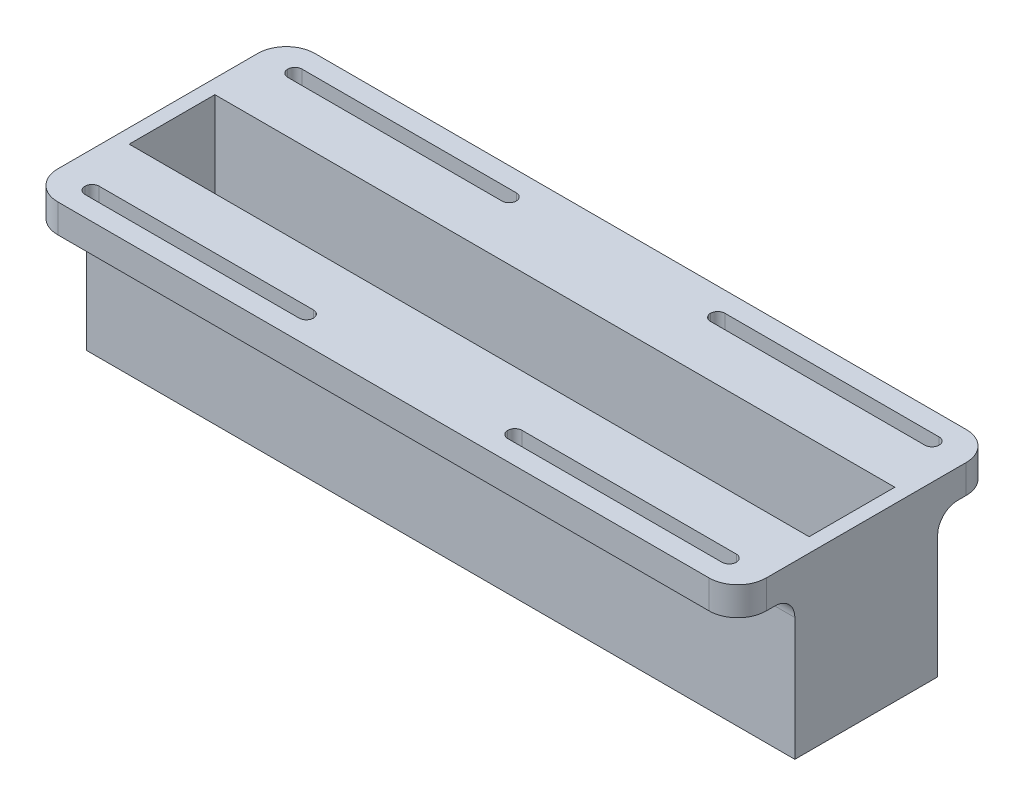
SolidWorks part; units mm, degrees
note: The reader was unsure of these and kept them because the rebuilt part matched: shared geometry of "Esquisse2<4>".
ref_plane "Plan de face" through (0, 0, 0) normal (0, 0, 1) x (1, 0, 0)
ref_plane "Plan de dessus" through (0, 0, 0) normal (0, 1, 0) x (1, 0, 0)
ref_plane "Plan de droite" through (0, 0, 0) normal (1, 0, 0) x (0, 0, -1)
sketch "Esquisse1" plane through (0, 0, 0) normal (0, 0, 1) x (1, 0, 0)
  line L1 (0, 0) -> (119, 0)
  line L2 (0, 0) -> (0, 61)
  line L3 (0, 61) -> (119, 61)
  line L4 (119, 0) -> (119, 61)
  line L5 (-2.5, -2.5) -> (121.5, -2.5)
  line L6 (-2.5, -2.5) -> (-2.5, 63.5)
  line L7 (-2.5, 63.5) -> (121.5, 63.5)
  line L8 (121.5, -2.5) -> (121.5, 63.5)
  dimension "D1" = 119
  dimension "D2" = 61
  dimension "D3" = 124
  dimension "D4" = 2.5
  dimension "D5" = 2.5
  dimension "D6" = 66
extrude "Boss.-Extru.1" add sketch "Esquisse1" along normal blind 15
sketch "Esquisse2" plane through (0, 0, 15) normal (0, 0, 1) x (1, 0, 0)
  line L0 (121.5, -2.5) -> (121.5, 63.5) construction
  line L1 (-2.5, -2.5) -> (121.5, -2.5)
  line L2 (-2.5, -2.5) -> (-2.5, 27.5)
  line L3 (-2.5, 27.5) -> (121.5, 27.5)
  line L4 (121.5, -2.5) -> (121.5, 27.5)
  line L6 (-2.5, 27.5) -> (121.5, 27.5)
  line L7 (-7.3247, 27.5) -> (134.2652, 27.5)
  line L8 (-7.3247, 27.5) -> (-7.3247, 70.1834)
  line L9 (-7.3247, 70.1834) -> (134.2652, 70.1834)
  line L10 (134.2652, 27.5) -> (134.2652, 70.1834)
  dimension "D1" = 30
extrude "Boss.-Extru.2" add sketch "Esquisse2" along normal blind 5
sketch "Esquisse3" plane through (0, 0, 0) normal (0, 0, -1) x (-1, 0, 0)
  line L0 (-121.5, -2.5) -> (-121.5, 63.5) construction
  line L1 (-121.5, 27.5) -> (2.5, 27.5)
  line L2 (-121.5, 27.5) -> (-121.5, -2.5)
  line L3 (-121.5, -2.5) -> (2.5, -2.5)
  line L4 (2.5, 27.5) -> (2.5, -2.5)
extrude "Boss.-Extru.3" add sketch "Esquisse3" along normal blind 5
extrude "Enlèv. mat.-Extru.2" cut sketch "Esquisse2<4>" against normal through all
sketch "Esquisse2<4>" plane through (0, 0, 15) normal (0, 0, 1) x (1, 0, 0) same geometry as "Esquisse2"
sketch "Esquisse4" plane through (0, 0, 20) normal (0, 0, 1) x (1, 0, 0)
  line L0 (-2.5, 27.5) -> (121.5, 27.5) construction
  line L1 (-2.5, 27.5) -> (121.5, 27.5)
  line L2 (-2.5, 27.5) -> (-2.5, 22.5)
  line L3 (-2.5, 22.5) -> (121.5, 22.5)
  line L4 (121.5, 27.5) -> (121.5, 22.5)
  line L5 (121.5, -2.5) -> (121.5, 27.5) construction
  dimension "D1" = 5
extrude "Boss.-Extru.4" add sketch "Esquisse4" along normal blind 10
sketch "Esquisse6" plane through (0, 0, -5) normal (0, 0, -1) x (-1, 0, 0)
  line L0 (2.5, -2.5) -> (2.5, 27.5) construction
  line L1 (-121.5, 27.5) -> (2.5, 27.5)
  line L2 (-121.5, 27.5) -> (-121.5, 22.5)
  line L3 (-121.5, 22.5) -> (2.5, 22.5)
  line L4 (2.5, 27.5) -> (2.5, 22.5)
  dimension "D1" = 5
extrude "Boss.-Extru.5" add sketch "Esquisse6" along normal blind 10
sketch "Esquisse5" plane through (0, 27.5, 0) normal (0, 1, 0) x (1, 0, 0)
  line L0 (121.5, -30) -> (-2.5, -30) construction
  line L1 (2.5, -26.5) -> (116.5, -26.5)
  line L2 (2.5, -26.5) -> (2.5, -24)
  line L3 (2.5, -24) -> (116.5, -24)
  line L4 (116.5, -26.5) -> (116.5, -24)
  line L5 (-2.5, -30) -> (-2.5, 15) construction
  line L6 (121.5, -30) -> (121.5, 15) construction
  line L7 (-2.5, -30) -> (-2.5, 15) construction
  line L8 (42.5, -24) -> (76.5, -24)
  line L9 (42.5, -24) -> (42.5, -26.5)
  line L10 (42.5, -26.5) -> (76.5, -26.5)
  line L11 (76.5, -24) -> (76.5, -26.5)
  line L12 (2.5, 11.5) -> (116.5, 11.5)
  line L13 (2.5, 11.5) -> (2.5, 9)
  line L14 (2.5, 9) -> (116.5, 9)
  line L15 (116.5, 11.5) -> (116.5, 9)
  line L16 (121.5, -30) -> (121.5, 15) construction
  line L17 (-2.5, 15) -> (121.5, 15) construction
  line L18 (42.5, 11.5) -> (76.5, 11.5)
  line L19 (42.5, 11.5) -> (42.5, 9)
  line L20 (42.5, 9) -> (76.5, 9)
  line L21 (76.5, 11.5) -> (76.5, 9)
  dimension "D1" = 2.5
  dimension "D2" = 3.5
  dimension "D3" = 5
  dimension "D4" = 5
  dimension "D5" = 40
  dimension "D6" = 40
  dimension "D7" = 5
  dimension "D8" = 5
  dimension "D9" = 40
  dimension "D10" = 40
  dimension "D11" = 2.5
  dimension "D12" = 3.5
extrude "Enlèv. mat.-Extru.3" cut sketch "Esquisse5" against normal blind 10 contours L9 L3 L2 L1 | L3 L11 L1 L4 | L19 L12 L13 L14 | L12 L21 L14 L15
fillet "Congé5" radius 5 4 edges at (121.5, 25, 30) (121.5, 25, -15) (-2.5, 25, -15) (-2.5, 25, 30)
fillet "Congé6" radius 3.5 2 edges
fillet "Congé7" radius 1.25 16 edges at (76.5, 25, -11.5) (76.5, 25, -9) (116.5, 25, -9) (116.5, 25, -11.5) (42.5, 25, -11.5) (42.5, 25, -9) (2.5, 25, -11.5) (2.5, 25, -9) (2.5, 25, 24) (2.5, 25, 26.5) (42.5, 25, 24) (42.5, 25, 26.5) (76.5, 25, 24) (76.5, 25, 26.5) (116.5, 25, 24) (116.5, 25, 26.5)
sketch "Esquisse7" plane through (0, 0, 0) normal (0, 1, 0) x (1, 0, 0)
  line L0 (0, -15) -> (119, -15) construction
  line L1 (116, 0) -> (79, 0)
  line L2 (116, 0) -> (116, -15)
  line L3 (116, -15) -> (79, -15)
  line L4 (79, 0) -> (79, -15)
  line L5 (119, -15) -> (119, 0) construction
  dimension "D1" = 3
  dimension "D2" = 40
extrude "Enlèv. mat.-Extru.4" cut sketch "Esquisse7" against normal through all
